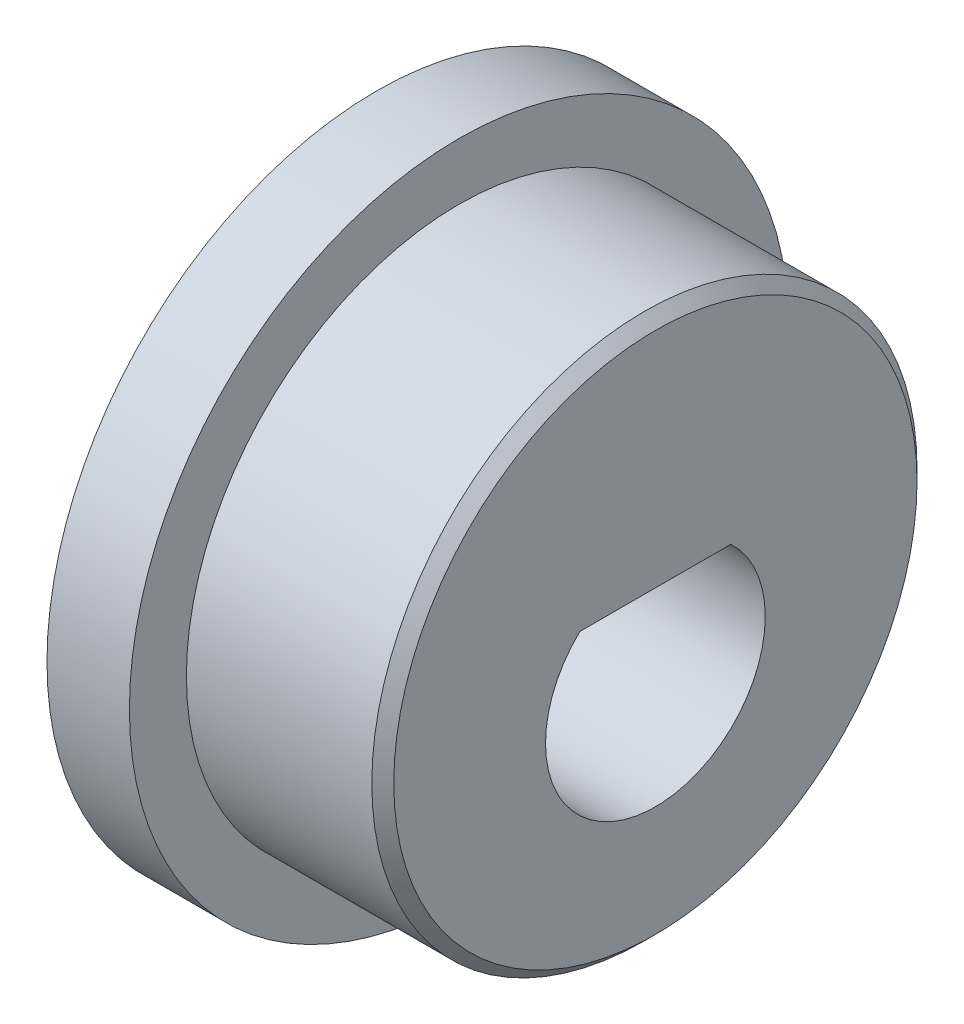
SolidWorks part; units mm, degrees
ref_plane "Ebene vorne" through (0, 0, 0) normal (0, 0, 1) x (1, 0, 0)
ref_plane "Ebene oben" through (0, 0, 0) normal (0, 1, 0) x (1, 0, 0)
ref_plane "Ebene rechts" through (0, 0, 0) normal (1, 0, 0) x (0, 0, -1)
sketch "Skizze1" plane through (0, 0, 0) normal (1, 0, 0) x (0, 0, -1)
  circle A0 centre (0, 1.5) radius 9.925
  point P2 (0, 0)
  dimension "D2" = 19.85
  dimension "D1" = 1.5
extrude "Aufsatz-Linear austragen1" add sketch "Skizze1" along normal blind 7.15
sketch "Skizze2" plane through (0, 0, 0) normal (-1, 0, 0) x (0, 0, 1)
  circle A0 centre (0, 1.5) radius 12
  dimension "D1" = 24
extrude "Aufsatz-Linear austragen2" add sketch "Skizze2" along normal blind 3
sketch "Skizze3" plane through (7.15, 0, 0) normal (1, 0, 0) x (0, 0, -1)
  line L0 (-2.75, 2.9047) -> (2.75, 2.9047)
  arc A0 (-2.75, 2.9047) -> (2.75, 2.9047) centre (0, 0) ccw
  dimension "D1" = 4
  dimension "D2" = 5.5
extrude "Schnitt-Linear austragen2" cut sketch "Skizze3" against normal through all both and the other way through all
chamfer "Fase1" distance 0.4 angle 45 1 edges at (7.15, 1.5, -9.925)
